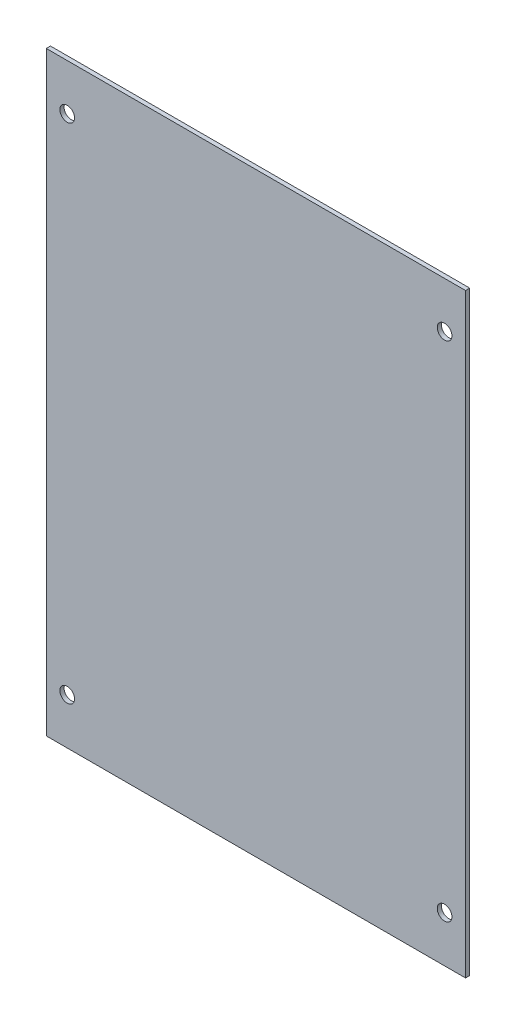
SolidWorks part; units mm, degrees
ref_plane "Front Plane" through (0, 0, 0) normal (0, 0, 1) x (1, 0, 0)
ref_plane "Top Plane" through (0, 0, 0) normal (0, 1, 0) x (1, 0, 0)
ref_plane "Right Plane" through (0, 0, 0) normal (1, 0, 0) x (0, 0, -1)
sketch "Sketch2" plane through (0, 0, 0) normal (0, 0, 1) x (1, 0, 0)
  line L1 (50, -65) -> (-50, -65)
  line L2 (50, -65) -> (50, 65)
  line L3 (50, 65) -> (-50, 65)
  line L4 (-50, -65) -> (-50, 65)
  line L5 (50, -65) -> (-50, 65) construction
  line L6 (50, 65) -> (-50, -65) construction
  point P0 (0, 0)
  dimension "D1" = 100
  dimension "D2" = 130
extrude "Boss-Extrude1" add sketch "Sketch2" along normal blind 1
sketch "Sketch3" plane through (0, 0, 0) normal (0, 0, -1) x (-1, 0, 0)
  line L0 (-50, -65) -> (-50, 65) construction
  line L1 (50, -65) -> (-50, -65) construction
  line L2 (0, 0.55) -> (0, -0.55) construction
  line L3 (0.55, 0) -> (-0.55, 0) construction
  circle A0 centre (-45, -60) radius 1.75
  circle A1 centre (45, -60) radius 1.75
  circle A2 centre (45, 60) radius 1.75
  circle A3 centre (-45, 60) radius 1.75
  dimension "D1" = 3.5
  dimension "D2" = 5
  dimension "D3" = 5
extrude "Cut-Extrude1" cut sketch "Sketch3" against normal blind 19
sketch "Sketch5" plane through (0, 65, 0) normal (0, 1, 0) x (1, 0, 0)
  line L1 (-50, -1) -> (50, -1)
  line L2 (-50, -1) -> (-50, 0)
  line L3 (-50, 0) -> (50, 0)
  line L4 (50, -1) -> (50, 0)
extrude "Boss-Extrude2" add sketch "Sketch5" along normal blind 6
mirror "Mirror1" about plane through (0, 0, 0) normal (0, 1, 0) of "Boss-Extrude2"
